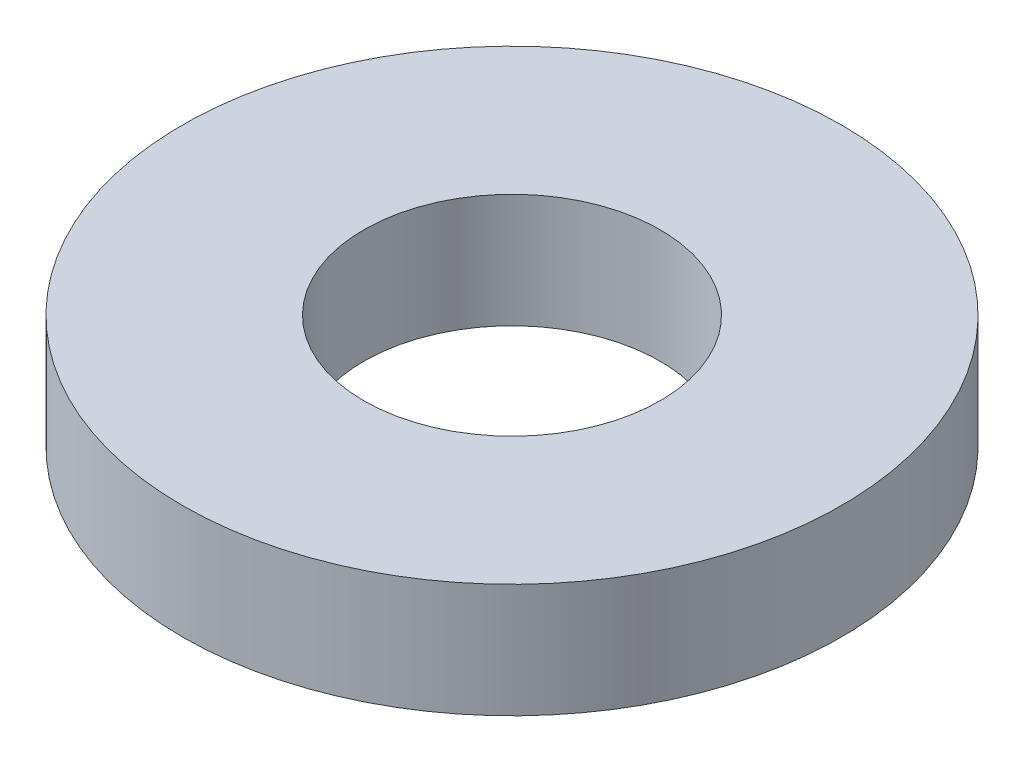
SolidWorks part; units mm, degrees
material "Plain Carbon Steel"
ref_plane "Front" through (0, 0, 0) normal (0, 0, 1) x (1, 0, 0)
ref_plane "Top" through (0, 0, 0) normal (0, 1, 0) x (1, 0, 0)
ref_plane "Right" through (0, 0, 0) normal (1, 0, 0) x (0, 0, -1)
ref_axis "Axis1" through (0, 0, 8.7312) along (0, 0, -1)
sketch "Sketch1" plane through (0, 0, 0) normal (0, 1, 0) x (1, 0, 0)
  circle A0 centre (0, 0) radius 3.5687
  circle A1 centre (0, 0) radius 7.9375
  dimension "D1" = 7.1374
  dimension "D2" = 15.875
extrude "Boss-Extrude1" add sketch "Sketch1" along normal blind 2.7432
